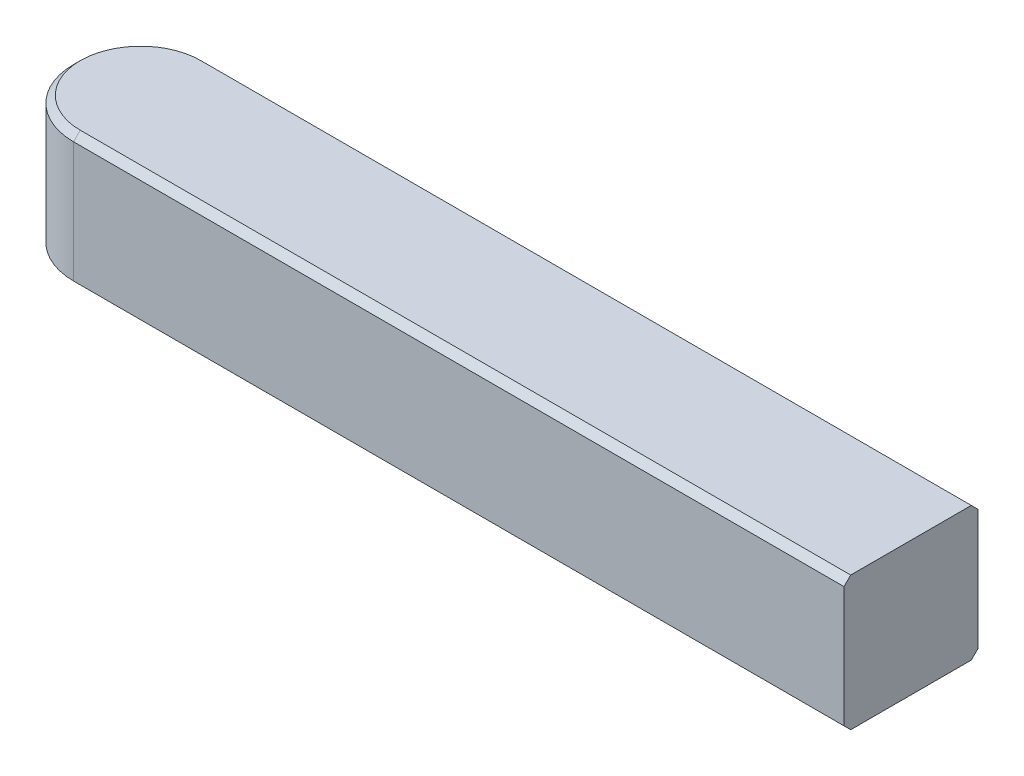
SolidWorks part; units mm, degrees
ref_plane "Front Plane" through (0, 0, 0) normal (0, 0, 1) x (1, 0, 0)
ref_plane "Top Plane" through (0, 0, 0) normal (0, 1, 0) x (1, 0, 0)
ref_plane "Right Plane" through (0, 0, 0) normal (1, 0, 0) x (0, 0, -1)
sketch "Sketch1" plane through (0, 0, 0) normal (0, 1, 0) x (1, 0, 0)
  line L0 (25, 0) -> (0, 0) construction
  line L4 (0, 2) -> (25, 2)
  line L5 (0, 2) -> (0, -2)
  line L6 (0, -2) -> (25, -2)
  line L7 (25, 2) -> (25, -2)
  dimension "FIX_1" = 4
  dimension "FIX_2" = 25
extrude "Boss-Extrude1" add sketch "Sketch1" along normal blind 4
fillet "Fillet1" 2 edges at (0, 2, -2) (0, 2, 2) type full round first side face at (12.5, 2, -2) second side face at (12.5, 2, 2) middle face at (0, 2, 0)
chamfer "Chamfer1" distance 0.2 angle 45 6 edges at (13.5, 4, -2) (0, 4, 0) (13.5, 4, 2) (13.5, 0, -2) (0, 0, 0) (13.5, 0, 2)
